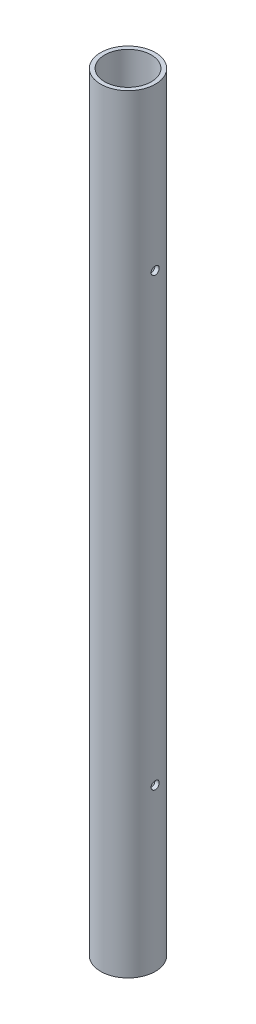
SolidWorks part; units mm, degrees
material "Copper"
ref_plane "Front Plane" through (0, 0, 0) normal (0, 0, 1) x (1, 0, 0)
ref_plane "Top Plane" through (0, 0, 0) normal (0, 1, 0) x (1, 0, 0)
ref_plane "Right Plane" through (0, 0, 0) normal (1, 0, 0) x (0, 0, -1)
sketch "Sketch1" plane through (0, 0, 0) normal (0, 0, 1) x (1, 0, 0)
  line L0 (0, -69.1907) -> (0, 69.1907) construction
  line L1 (0, 0) -> (111.878, 0) construction
  line L2 (9.4615, -155.956) -> (11.1125, -155.956)
  line L3 (9.4615, -155.956) -> (9.4615, 155.956)
  line L4 (9.4615, 155.956) -> (11.1125, 155.956)
  line L5 (11.1125, -155.956) -> (11.1125, 155.956)
  line L6 (9.4615, -155.956) -> (11.1125, 155.956) construction
  line L7 (9.4615, 155.956) -> (11.1125, -155.956) construction
  point P0 (10.287, 0)
  point P4 (0, 0)
  dimension "D1" = 11.1125
  dimension "D2" = 1.651
revolve "Revolve1" add sketch "Sketch1" angle 360 about L0
ref_plane "Plane1" through (11.1125, 0, 0) normal (1, 0, 0) x (0, 0, -1)
hole_wizard "#4 Clearance Hole1" positions "Sketch2" profile "Sketch3" hole size "#4" standard "ANSI Inch" end condition through all
sketch "Sketch2" plane through (11.1125, 0, 0) normal (1, 0, 0) x (0, 0, -1)
  line L0 (9.4615, 155.956) -> (-9.4615, 155.956) construction
  line L1 (0, 155.956) -> (0, -155.956) construction
  line L2 (11.1125, 155.956) -> (-11.1125, 155.956) construction
  line L3 (-11.1125, -155.956) -> (11.1125, -155.956) construction
  point P0 (0, 90.4545)
  point P2 (0, -90.4545)
sketch "Sketch3" plane through (11.1125, 90.4545, 0) normal (0, 1, 0) x (0, 0, -1)
  line L0 (0, 0) -> (0, 22.225)
  line L1 (0, 22.225) -> (1.6319, 22.225)
  line L2 (1.6319, 22.225) -> (1.6319, 0)
  line L5 (1.6319, 0) -> (0, 0)
  line L11 (0, -6.35) -> (0, 107.95) construction
  dimension "Thru Hole Dia." = 3.2639
  dimension "Thru Hole Depth" = 22.225
ref_plane "Plane2" [suppressed] through (0, 0, 0) normal (0, -1, 0) x (-1, 0, 0)
equation "\"h1\"= .21in"
equation "\"h2\"= .79in"
equation "\"D1@Sketch2\"=\"L\"*\"h1\""
equation "\"D2@Sketch2\"=\"L\"*\"h2\""
